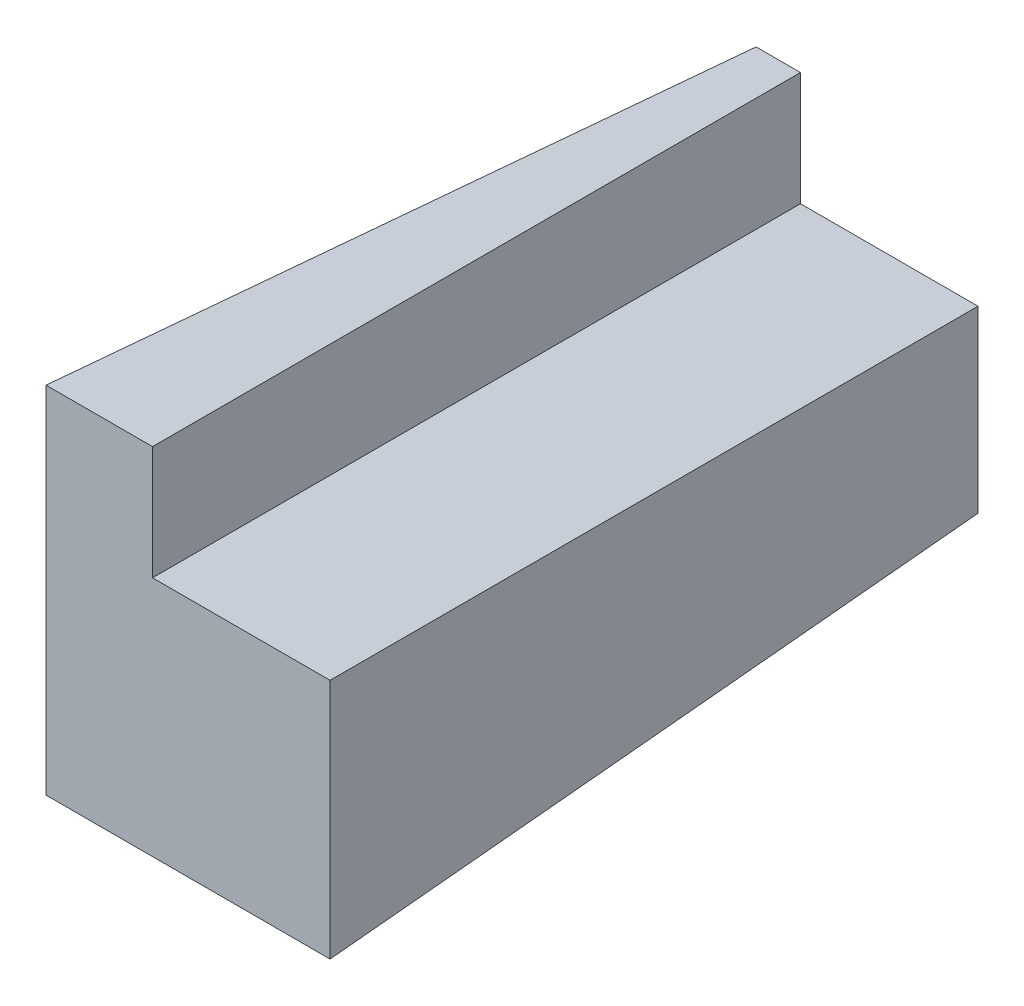
SolidWorks part; units mm, degrees
ref_plane "Front Plane" through (0, 0, 0) normal (0, 0, 1) x (1, 0, 0)
ref_plane "Top Plane" through (0, 0, 0) normal (0, 1, 0) x (1, 0, 0)
ref_plane "Right Plane" through (0, 0, 0) normal (1, 0, 0) x (0, 0, -1)
sketch "Sketch2" plane through (0, 0, 0) normal (0, 0, 1) x (1, 0, 0)
  line L0 (0, 0) -> (0, 10)
  line L1 (0, 10) -> (3, 10)
  line L2 (3, 10) -> (3, 6.8)
  line L3 (3, 6.8) -> (8, 6.8)
  line L4 (8, 6.8) -> (8, 0)
  line L5 (8, 0) -> (0, 0)
extrude "Boss-Extrude1" add sketch "Sketch2" along normal blind 50
draft "Draft7" type of draft neutral plane draft angle 5 faces to draft 4 face at (8, 3.4, 25) face at (5.5, 6.8, 25) face at (3, 8.4, 25) face at (1.5, 10, 25) neutral plane through (0, 0, 50) neutral plane normal (0, 0, 1) reverse direction yes parameters "D1"=5
sketch "Sketch3" plane through (0, 0, 0) normal (0, 0, -1) x (-1, 0, 0)
  line L1 (0, 0) -> (-8.6066, 0)
  line L2 (0, 0) -> (0, 8.7323)
  line L3 (0, 8.7323) -> (-8.6066, 8.7323)
  line L4 (-8.6066, 0) -> (-8.6066, 8.7323)
extrude "Cut-Extrude1" cut sketch "Sketch3" against normal blind 30
